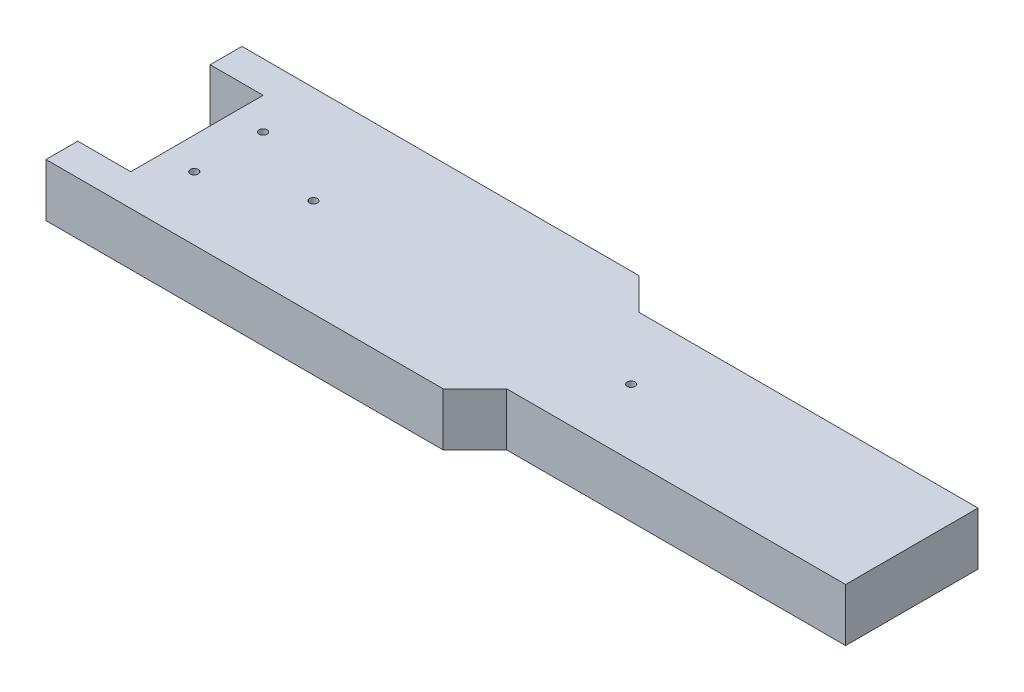
SolidWorks part; units mm, degrees
material "Сосна"
ref_plane "Спереди" through (0, 0, 0) normal (0, 0, 1) x (1, 0, 0)
ref_plane "Сверху" through (0, 0, 0) normal (0, 1, 0) x (1, 0, 0)
ref_plane "Справа" through (0, 0, 0) normal (1, 0, 0) x (0, 0, -1)
sketch "Эскиз1" plane through (0, 0, 0) normal (0, 1, 0) x (1, 0, 0)
  line L0 (0, 31) -> (75, 31)
  line L1 (75, 31) -> (81, 25)
  line L2 (81, 25) -> (145, 25)
  line L3 (145, 25) -> (145, 0)
  line L4 (145, 0) -> (81, 0)
  line L5 (81, 0) -> (75, -6)
  line L6 (75, -6) -> (0, -6)
  line L7 (0, -6) -> (0, 0)
  line L8 (0, 0) -> (10, 0)
  line L9 (10, 0) -> (10, 25)
  line L10 (10, 25) -> (0, 25)
  line L11 (0, 25) -> (0, 31)
  dimension "D1" = 145
  dimension "D2" = 75
  dimension "D3" = 25
  dimension "D4" = 25
  dimension "D5" = 37
  dimension "D6" = 10
extrude "Бобышка-Вытянуть1" add sketch "Эскиз1" along normal blind 10
sketch "Эскиз2" plane through (0, 10, 0) normal (0, 1, 0) x (1, 0, 0)
  line L0 (0, 31) -> (0, 25) construction
  line L1 (75, 31) -> (0, 31) construction
  circle A0 centre (32, 12.5) radius 0.75
  dimension "D1" = 1.5
  dimension "D2" = 32
  dimension "D3" = 18.5
extrude "Вырез-Вытянуть1" cut sketch "Эскиз2" against normal through all
pattern_linear "Линейный массив1" count 2 spacing 60 along (1, 0, 0) of "Вырез-Вытянуть1"
sketch "Эскиз3" plane through (0, 10, 0) normal (0, 1, 0) x (1, 0, 0)
  line L1 (0, 0) -> (0, -6) construction
  line L2 (0, -6) -> (75, -6) construction
  circle A0 centre (16, 6) radius 0.75
  circle A1 centre (16, 19) radius 0.75
  dimension "D1" = 16
  dimension "D4" = 1.5
  dimension "D2" = 12
  dimension "D3" = 2
extrude "Вырез-Вытянуть2" cut sketch "Эскиз3" against normal through all
